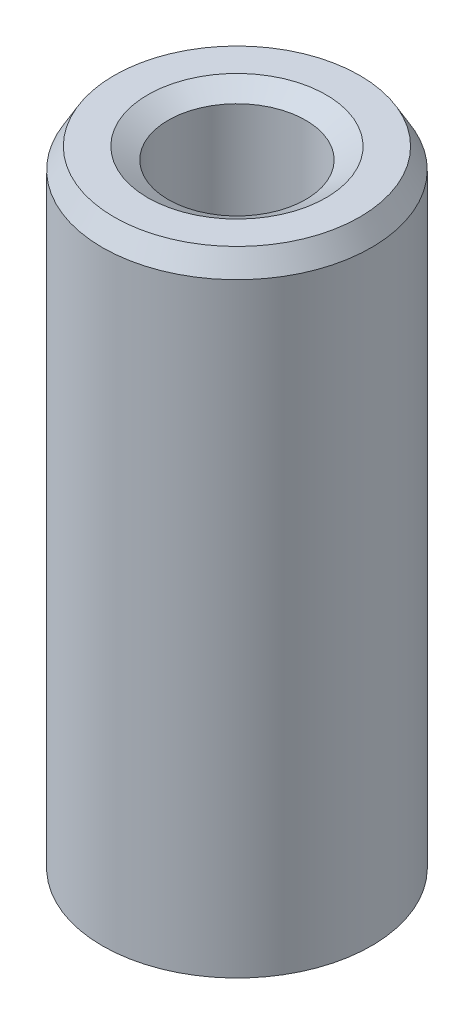
SolidWorks part; units mm, degrees
ref_plane "Front Plane" through (0, 0, 0) normal (0, 0, 1) x (1, 0, 0)
ref_plane "Top Plane" through (0, 0, 0) normal (0, 1, 0) x (1, 0, 0)
ref_plane "Right Plane" through (0, 0, 0) normal (1, 0, 0) x (0, 0, -1)
sketch "Sketch1" plane through (0, 0, 0) normal (0, 1, 0) x (1, 0, 0)
  circle A0 centre (0, 0) radius 7.5
  dimension "SLEEVE_OD" = 15
extrude "Boss-Extrude1" add sketch "Sketch1" along normal blind 35.5001
sketch "Sketch2" plane through (0, 0, 0) normal (0, 1, 0) x (1, 0, 0)
  circle A0 centre (0, 0) radius 3.8319
  dimension "BORE_D" = 7.6638
extrude "Cut-Extrude1" cut sketch "Sketch2" along normal through all
chamfer "Chamfer1" distance 1.1393 angle 30 4 edges at (0, 35.5001, 3.8319) (0, 0, 3.8319) (0, 0, 7.5) (0, 35.5001, 7.5) first distance on face at (0, 35.5001, 3.8319) first distance on face at (0, 0, 3.8319) first distance on face at (0, 35.5001, 7.5)
